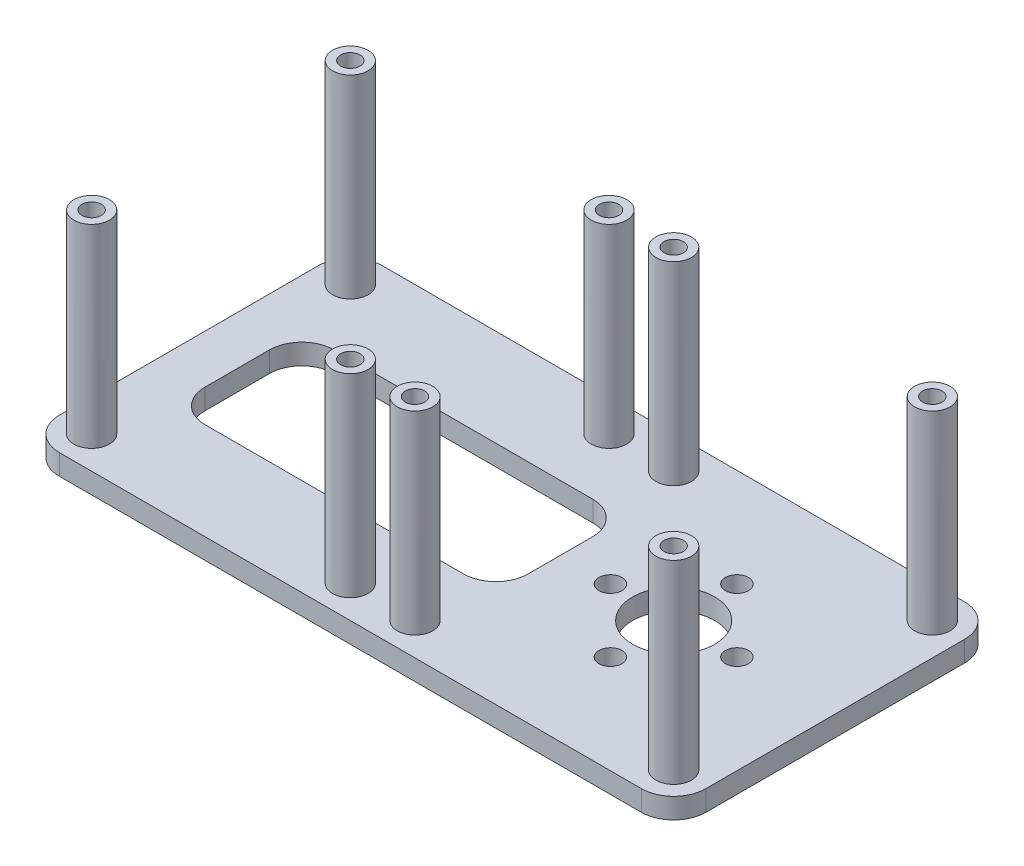
SolidWorks part; units mm, degrees
material "Copper"
ref_plane "Front Plane" through (0, 0, 0) normal (0, 0, 1) x (1, 0, 0)
ref_plane "Top Plane" through (0, 0, 0) normal (0, 1, 0) x (1, 0, 0)
ref_plane "Right Plane" through (0, 0, 0) normal (1, 0, 0) x (0, 0, -1)
sketch "Sketch1" plane through (0, 0, 0) normal (0, 1, 0) x (1, 0, 0)
  line L1 (-25, -25) -> (25, -25)
  line L2 (-25, -25) -> (-25, 25)
  line L3 (-25, 25) -> (25, 25)
  line L4 (25, -25) -> (25, 25)
  line L5 (-25, -25) -> (25, 25) construction
  line L6 (-25, 25) -> (25, -25) construction
  circle A0 centre (0, 0) radius 6.35
  circle A1 centre (-9.779, 0) radius 1.778
  circle A2 centre (9.779, 0) radius 1.778
  circle A3 centre (0, 9.779) radius 1.778
  circle A4 centre (0, -9.779) radius 1.778
  point P0 (0, 0)
  dimension "D3" = 12.7
  dimension "D8" = 3.556
  dimension "D9" = 3.556
  dimension "D10" = 3.556
  dimension "D11" = 3.556
  dimension "D1" = 50
  dimension "D2" = 50
  dimension "D4" = 9.779
  dimension "D5" = 9.779
  dimension "D6" = 9.779
  dimension "D7" = 9.779
extrude "Boss-Extrude1" add sketch "Sketch1" along normal blind 3.175
sketch "Sketch2" plane through (0, 3.175, 0) normal (0, 1, 0) x (1, 0, 0)
  line L0 (25, 25) -> (-25, 25) construction
  line L1 (-25, 25) -> (-25, -25) construction
  line L2 (25, -25) -> (25, 25) construction
  line L3 (-25, -25) -> (25, -25) construction
  circle A0 centre (20, -20) radius 2.75
  circle A1 centre (-20, -20) radius 2.75
  circle A2 centre (-20, 20) radius 2.75
  circle A3 centre (20, 20) radius 2.75
  circle A4 centre (-20, -20) radius 1.5
  circle A5 centre (20, -20) radius 1.5
  circle A6 centre (-20, 20) radius 1.5
  circle A7 centre (20, 20) radius 1.5
  dimension "D1" = 5
  dimension "D9" = 3
  dimension "D10" = 5.5
  dimension "D11" = 3
  dimension "D12" = 5.5
  dimension "D13" = 3
  dimension "D14" = 5.5
  dimension "D15" = 3
  dimension "D16" = 5.5
  dimension "D2" = 5
  dimension "D3" = 5
  dimension "D4" = 5
  dimension "D5" = 5
  dimension "D6" = 5
  dimension "D7" = 5
  dimension "D8" = 5
extrude "Boss-Extrude2" add sketch "Sketch2" along normal blind 30
sketch "Sketch3" plane through (0, 0, 0) normal (0, 1, 0) x (1, 0, 0)
  line L1 (-25, 25) -> (-75, 25)
  line L2 (-25, 25) -> (-25, -25)
  line L3 (-25, -25) -> (-75, -25)
  line L4 (-75, 25) -> (-75, -25)
  dimension "D1" = 50
  dimension "D2" = 50
extrude "Boss-Extrude3" add sketch "Sketch3" along normal up to surface (3.175 mm away) up to face at (20, 3.175, -22.75)
sketch "Sketch4" plane through (0, 3.175, 0) normal (0, 1, 0) x (1, 0, 0)
  line L0 (-75, -25) -> (-75, 25) construction
  line L1 (25, 25) -> (-75, 25) construction
  line L2 (-75, -25) -> (25, -25) construction
  circle A0 centre (-70, 20) radius 2.75
  circle A1 centre (-30, 20) radius 1.5
  circle A2 centre (-70, -20) radius 2.75
  circle A3 centre (-30, -20) radius 2.75
  circle A4 centre (-30, -20) radius 1.5
  circle A5 centre (-70, -20) radius 1.5
  circle A6 centre (-70, 20) radius 1.5
  circle A7 centre (-30, 20) radius 2.75
  circle A8 centre (-20, 20) radius 2.75 construction
  circle A9 centre (-20, -20) radius 1.5 construction
  dimension "D6" = 3
  dimension "D7" = 5.5
  dimension "D8" = 3
  dimension "D9" = 5.5
  dimension "D12" = 3
  dimension "D13" = 5.5
  dimension "D14" = 5.5
  dimension "D15" = 3
  dimension "D1" = 5
  dimension "D2" = 5
  dimension "D3" = 5
  dimension "D4" = 10
  dimension "D5" = 10
  dimension "D10" = 5
  dimension "D11" = 5
  dimension "D16" = 5
extrude "Boss-Extrude4" add sketch "Sketch4" along normal blind 30
sketch "Sketch5" plane through (0, 3.175, 0) normal (0, 1, 0) x (1, 0, 0)
  line L0 (-75, -25) -> (-75, 25) construction
  line L1 (-67.5, 10) -> (-17.5, 10)
  line L2 (-67.5, 10) -> (-67.5, -10)
  line L3 (-67.5, -10) -> (-17.5, -10)
  line L4 (-17.5, 10) -> (-17.5, -10)
  line L5 (-75, -25) -> (25, -25) construction
  point P6 (-75, 0)
  dimension "D1" = 20
  dimension "D2" = 50
  dimension "D3" = 7.5
  dimension "D4" = 15
extrude "Cut-Extrude1" cut sketch "Sketch5" against normal blind 10
fillet "Fillet1" radius 5 8 edges at (-75, 1.5875, -25) (25, 1.5875, -25) (25, 1.5875, 25) (-75, 1.5875, 25) (-17.5, 1.5875, 10) (-17.5, 1.5875, -10) (-67.5, 1.5875, 10) (-67.5, 1.5875, -10)
